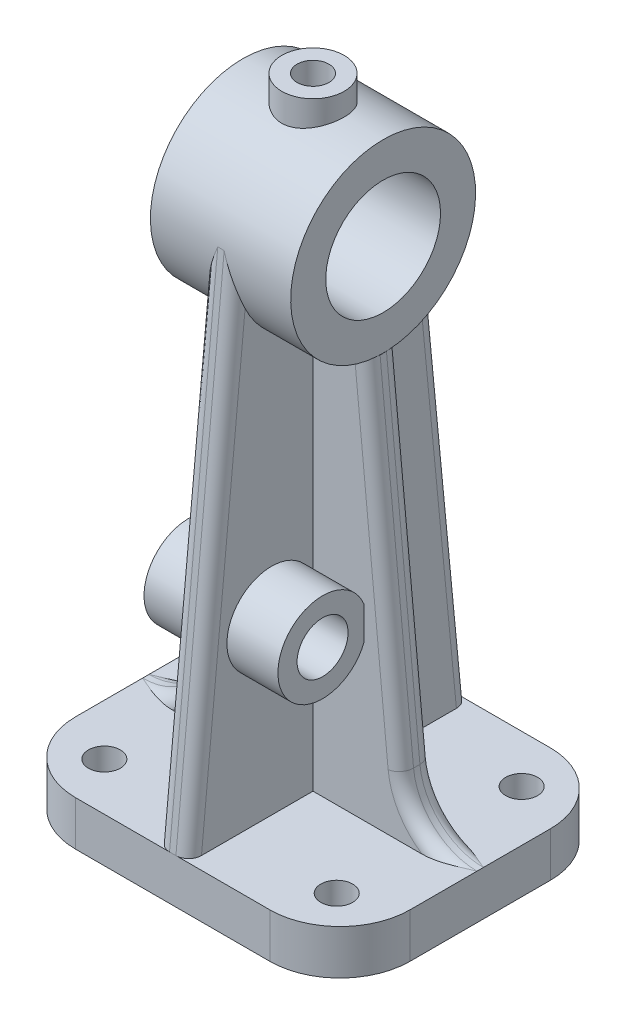
SolidWorks part; units mm, degrees
ref_plane "Front Plane" through (0, 0, 0) normal (0, 0, 1) x (1, 0, 0)
ref_plane "Top Plane" through (0, 0, 0) normal (0, 1, 0) x (1, 0, 0)
ref_plane "Right Plane" through (0, 0, 0) normal (1, 0, 0) x (0, 0, -1)
sketch "Sketch1" plane through (0, 0, 0) normal (0, 1, 0) x (1, 0, 0)
  line L0 (0, 34.925) -> (0, -34.925) construction
  line L1 (24.1653, 34.925) -> (-24.1653, 34.925)
  line L2 (41.6278, 17.4625) -> (41.6278, -17.4625)
  line L3 (24.1653, -34.925) -> (-24.1653, -34.925)
  line L4 (-41.6278, 17.4625) -> (-41.6278, -17.4625)
  line L5 (41.6278, 34.925) -> (-41.6278, -34.925) construction
  line L6 (41.6278, -34.925) -> (-41.6278, 34.925) construction
  line L7 (-41.6278, 0) -> (41.6278, 0) construction
  line L8 (-24.959, 23.0187) -> (24.959, 23.0188) construction
  arc A0 (-24.1653, -34.925) -> (-41.6278, -17.4625) centre (-24.1653, -17.4625) cw
  arc A1 (41.6278, -17.4625) -> (24.1653, -34.925) centre (24.1653, -17.4625) cw
  arc A2 (24.1653, 34.925) -> (41.6278, 17.4625) centre (24.1653, 17.4625) cw
  arc A3 (-24.1653, 34.925) -> (-41.6278, 17.4625) centre (-24.1653, 17.4625) ccw
  circle A4 centre (-28.9278, 23.0188) radius 3.9688
  circle A5 centre (28.9278, 23.0188) radius 3.9687
  circle A6 centre (28.9278, -23.0188) radius 3.9687
  circle A7 centre (-28.9278, -23.0188) radius 3.9688
  point P0 (0, 0)
  point P28 (0, 23.0188)
  dimension "D3" = 17.4625
  dimension "D5" = 7.9375
  dimension "D1" = 69.85
  dimension "D2" = 83.2556
  dimension "D4" = 57.8556
  dimension "D6" = 23.0188
extrude "Boss-Extrude1" add sketch "Sketch1" along normal blind 11.1125
sketch "Sketch3" plane through (0, 0, 0) normal (1, 0, 0) x (0, 0, -1)
  circle A0 centre (0, 133.35) radius 23.0188
  circle A1 centre (0, 133.35) radius 14.2875
  dimension "D1" = 46.0375
  dimension "D2" = 28.575
  dimension "D3" = 133.35
extrude "Boss-Extrude3" add sketch "Sketch3" along normal mid plane 34.925
sketch "Sketch4" plane through (0, 11.1125, 0) normal (0, 1, 0) x (1, 0, 0)
  line L0 (-41.6278, 17.4625) -> (-41.6278, -17.4625) construction
  line L1 (-41.6278, 3.9687) -> (41.6278, 3.9688)
  line L2 (-41.6278, 3.9687) -> (-41.6278, -3.9688)
  line L3 (-41.6278, -3.9688) -> (41.6278, -3.9688)
  line L4 (41.6278, 3.9688) -> (41.6278, -3.9688)
  line L5 (41.6278, -17.4625) -> (41.6278, 17.4625) construction
  point P8 (41.6278, 0)
  point P9 (41.6278, 0)
  dimension "D1" = 7.9375
extrude "Boss-Extrude4" add sketch "Sketch4" along normal up to surface (99.5635 mm away) up to face at (17.4625, 133.35, -23.0188)
sketch "Sketch5" plane through (0, 0, 3.9688) normal (0, 0, 1) x (1, 0, 0)
  line L0 (-41.6278, 110.676) -> (-41.6278, 11.1125) construction
  line L1 (-24.1653, 11.1125) -> (-41.6278, 11.1125) construction
  line L2 (-25.8287, 25.4368) -> (-17.4625, 110.676)
  line L3 (0, 110.676) -> (0, 0) construction
  line L4 (-17.4625, 110.676) -> (17.4625, 110.676) construction
  line L5 (-41.6278, 11.1125) -> (-41.6278, 110.676)
  line L6 (-41.6278, 110.676) -> (-17.4625, 110.676)
  line L7 (41.6278, 110.676) -> (17.4625, 110.676)
  line L8 (41.6278, 11.1125) -> (41.6278, 110.676)
  line L9 (25.8287, 25.4368) -> (17.4625, 110.676)
  arc A0 (-41.6278, 11.1125) -> (-25.8287, 25.4368) centre (-41.6278, 26.9875) ccw
  arc A1 (41.6278, 11.1125) -> (25.8287, 25.4368) centre (41.6278, 26.9875) cw
  dimension "D1" = 31.75
extrude "Cut-Extrude1" cut sketch "Sketch5" against normal through all
sketch "Sketch6" plane through (0, 0, 0) normal (1, 0, 0) x (0, 0, -1)
  line L0 (-34.925, 11.1125) -> (-22.9123, 135.5617)
  line L1 (0, 0) -> (0, 156.3688) construction
  line L2 (-17.4625, 0) -> (17.4625, 0) construction
  line L3 (34.925, 11.1125) -> (22.9123, 135.5617)
  line L4 (-3.9688, 110.676) -> (-3.9688, 11.1125)
  line L5 (-3.9688, 11.1125) -> (-34.925, 11.1125)
  line L6 (3.9688, 110.676) -> (3.9688, 11.1125)
  line L7 (3.9688, 11.1125) -> (34.925, 11.1125)
  arc A0 (3.9688, 110.676) -> (-3.9688, 110.676) centre (0, 133.35) ccw construction
  arc A1 (-22.9123, 135.5617) -> (22.9123, 135.5617) centre (0, 133.35) ccw
extrude "Boss-Extrude5" add sketch "Sketch6" along normal mid plane 7.9375 contours A1 L0 L5 L4 | A1 L6 L7 L3 region at (0, 60.71, -17.2969) region at (0, 60.71, 17.2969)
fillet "Fillet4" radius 3.175 12 edges at (-21.6456, 68.0564, 3.9688) (-21.6456, 68.0564, -3.9687) (-3.9688, 73.3371, -28.9186) (3.9688, 73.3371, -28.9186) (21.6456, 68.0564, -3.9688) (21.6456, 68.0564, 3.9688) (-3.9688, 73.3371, 28.9186) (3.9688, 73.3371, 28.9186)
sketch "Sketch7" plane through (0, 0, 0) normal (1, 0, 0) x (0, 0, -1)
  circle A0 centre (-14.2875, 53.6581) radius 6.35
  circle A1 centre (-14.2875, 53.6581) radius 11.1125
  circle A2 centre (0, 133.35) radius 80.9625 construction
  dimension "D1" = 12.7
  dimension "D2" = 22.225
  dimension "D4" = 161.925
  dimension "D3" = 14.2875
extrude "Boss-Extrude6" add sketch "Sketch7" along normal mid plane 33.3375
ref_plane "Plane1" through (0, 156.3688, 0) normal (0, 1, 0) x (1, 0, 0)
sketch "Sketch8" plane through (0, 156.3688, 0) normal (0, 1, 0) x (1, 0, 0)
  circle A0 centre (0, 0) radius 7.7611
  circle A1 centre (0, 0) radius 3.9688
  dimension "D1" = 15.5222
  dimension "D2" = 7.9375
extrude "Boss-Extrude7" add sketch "Sketch8" along normal blind 5.5562 and the other way up to surface separate body other way up to face at (0, 122.0446, 0)
extrude "Cut-Extrude2" cut sketch "Sketch8<2>" against normal up to surface (9.2935 mm away) contours A1 region at (0, 156.3688, 0) up to face at (17.4625, 133.35, -14.2875)
sketch "Sketch8<2>" plane through (0, 156.3688, 0) normal (0, 1, 0) x (1, 0, 0) same geometry as "Sketch8"
